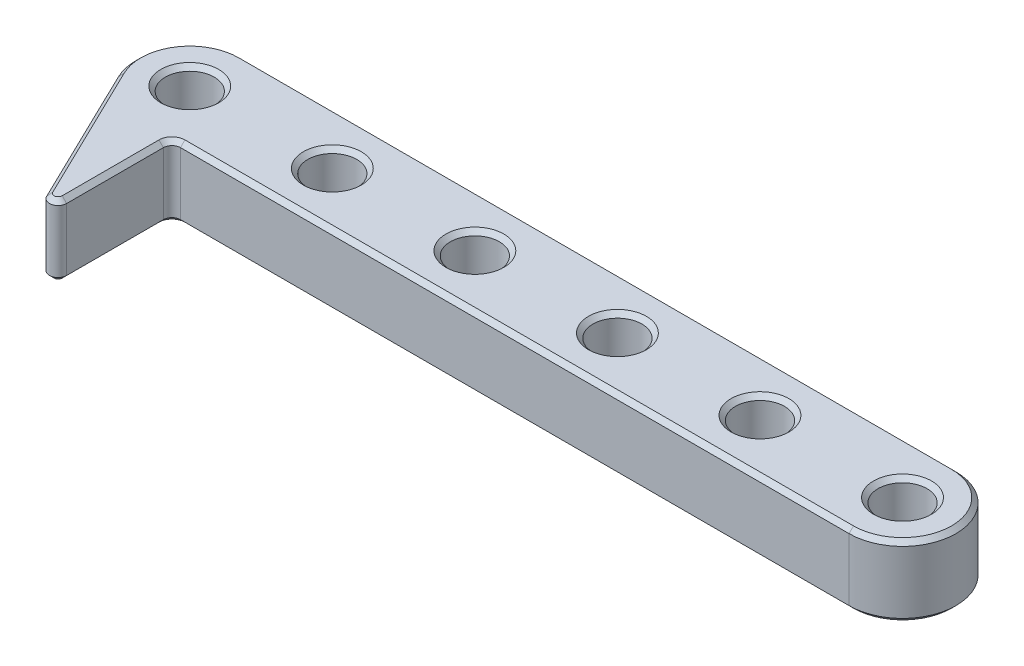
SolidWorks part; units mm, degrees
ref_plane "Front Plane" through (0, 0, 0) normal (0, 0, 1) x (1, 0, 0)
ref_plane "Top Plane" through (0, 0, 0) normal (0, 1, 0) x (1, 0, 0)
ref_plane "Right Plane" through (0, 0, 0) normal (1, 0, 0) x (0, 0, -1)
sketch "Sketch1" plane through (0, 0, 0) normal (0, 1, 0) x (1, 0, 0)
  line L0 (-63.5, 4.7625) -> (0, 4.7625)
  line L1 (0, -4.7625) -> (-59.563, -4.7625)
  line L2 (-60.325, -5.5245) -> (-60.325, -14.1447)
  line L3 (-67.7852, -2.078) -> (-61.7726, -14.4772)
  circle A0 centre (0, 0) radius 2.1828
  circle A1 centre (-63.5, 0) radius 2.1828
  arc A2 (0, -4.7625) -> (0, 4.7625) centre (0, 0) ccw
  arc A3 (-63.5, 4.7625) -> (-67.7852, -2.078) centre (-63.5, 0) ccw
  arc A4 (-60.325, -14.1447) -> (-61.7726, -14.4772) centre (-61.087, -14.1447) cw
  arc A5 (-59.563, -4.7625) -> (-60.325, -5.5245) centre (-59.563, -5.5245) ccw
  circle A6 centre (-12.7, 0) radius 2.1828
  circle A7 centre (-50.8, 0) radius 2.1828
  circle A8 centre (-25.4, 0) radius 2.1828
  circle A9 centre (-38.1, 0) radius 2.1828
  point P14 (-60.325, -17.4625)
  point P24 (0, 0)
  dimension "D2" = 4.3656
  dimension "D3" = 4.3656
  dimension "D4" = 9.525
  dimension "D5" = 9.525
  dimension "D8" = 0.762
  dimension "D9" = 0.762
  dimension "D11" = 4.3656
  dimension "D13" = 4.3656
  dimension "D15" = 4.3656
  dimension "D17" = 4.3656
  dimension "D1" = 63.5
  dimension "D6" = 12.7
  dimension "D7" = 60.325
  dimension "D10" = 12.7
  dimension "D12" = 12.7
  dimension "D14" = 12.7
  dimension "D16" = 12.7
extrude "Boss-Extrude1" add sketch "Sketch1" along normal blind 6.35
chamfer "Chamfer1" distance 0.3969 angle 45 28 edges at (-50.8, 0, 2.1828) (-12.7, 0, 2.1828) (-63.5, 0, 2.1828) (0, 0, 2.1828) (-64.7789, 0, 8.2776) (-60.9164, 0, 14.8874) (-60.325, 0, 9.8346) (-60.1018, 0, 4.9857) (-29.7815, 0, 4.7625) (4.7625, 0, 0) (-31.75, 0, -4.7625) (-67.536, 0, -2.5283) (-50.8, 6.35, 2.1828) (-63.5, 6.35, 2.1828) (-31.75, 6.35, -4.7625) (4.7625, 6.35, 0) (-29.7815, 6.35, 4.7625) (-60.1018, 6.35, 4.9857) (-60.325, 6.35, 9.8346) (-60.9164, 6.35, 14.8874) (-64.7789, 6.35, 8.2776) (-67.536, 6.35, -2.5283) (0, 6.35, 2.1828) (-12.7, 6.35, 2.1828) (-25.4, 0, 2.1828) (-38.1, 0, 2.1828) (-25.4, 6.35, 2.1828) (-38.1, 6.35, 2.1828)
